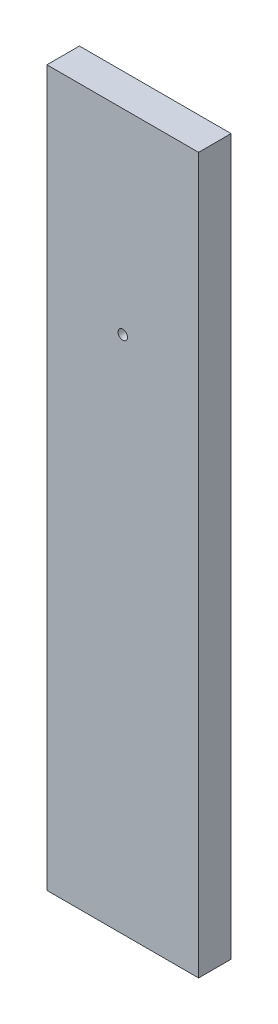
SolidWorks part; units mm, degrees
ref_plane "Front Plane" through (0, 0, 0) normal (0, 0, 1) x (1, 0, 0)
ref_plane "Top Plane" through (0, 0, 0) normal (0, 1, 0) x (1, 0, 0)
ref_plane "Right Plane" through (0, 0, 0) normal (1, 0, 0) x (0, 0, -1)
sketch "Sketch1" plane through (0, 0, 0) normal (0, 1, 0) x (1, 0, 0)
  line L1 (0, 0) -> (88.9, 0)
  line L2 (0, 0) -> (0, 19.05)
  line L3 (0, 19.05) -> (88.9, 19.05)
  line L4 (88.9, 0) -> (88.9, 19.05)
  dimension "D1" = 19.05
  dimension "D2" = 88.9
extrude "Boss-Extrude1" add sketch "Sketch1" along normal blind 419.1
sketch "Sketch2" plane through (0, 0, 0) normal (0, 0, 1) x (1, 0, 0)
  line L0 (44.45, 419.1) -> (44.45, 304.3258) construction
  line L1 (0, 419.1) -> (88.9, 419.1) construction
  line L2 (-349.25, 393.7) -> (44.45, 304.3258) construction
  line L3 (-349.25, 393.7) -> (-39.4224, 393.7) construction
  circle A0 centre (44.45, 304.3258) radius 2.7781
  circle A1 centre (-349.25, 393.7) radius 2.7781 construction
  circle A2 centre (-349.25, 393.7) radius 2.7781 construction
  dimension "D1" = 5.5562
  dimension "D2" = 12.79
extrude "Cut-Extrude1" cut sketch "Sketch2" against normal through all
